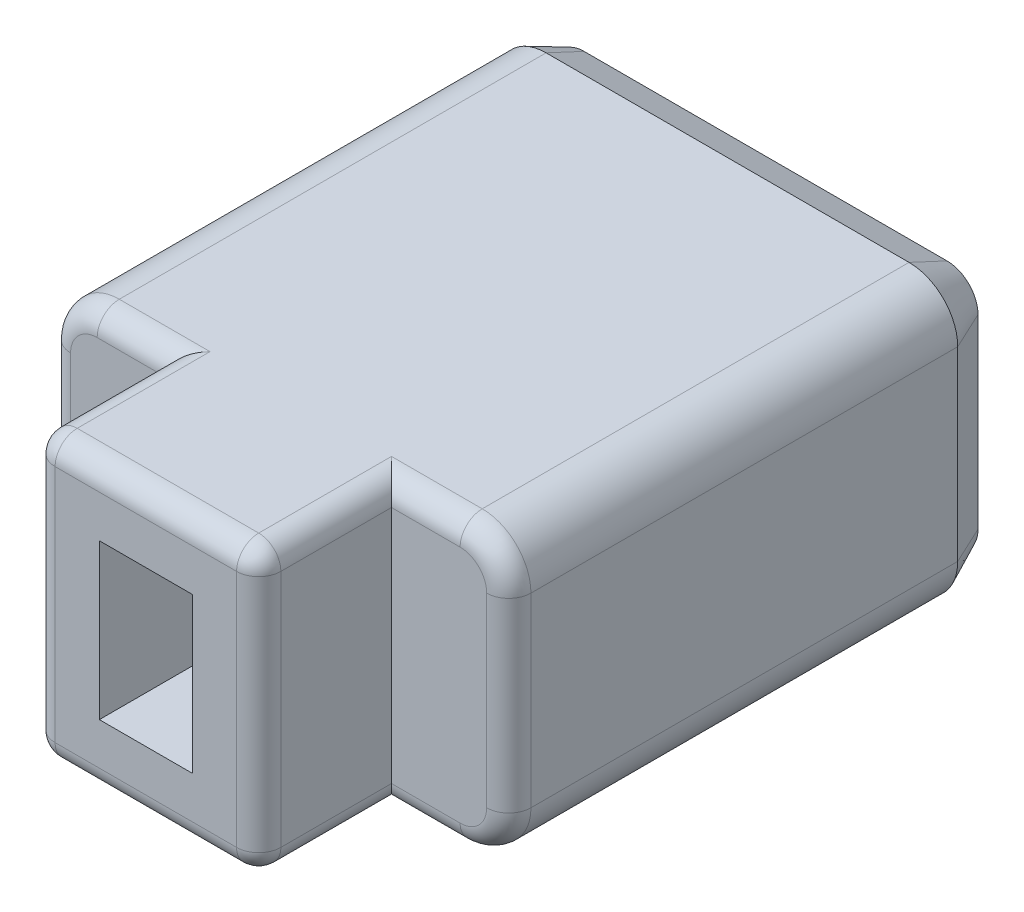
SolidWorks part; units mm, degrees
ref_plane "Plan de face" through (0, 0, 0) normal (0, 0, 1) x (1, 0, 0)
ref_plane "Plan de dessus" through (0, 0, 0) normal (0, 1, 0) x (1, 0, 0)
ref_plane "Plan de droite" through (0, 0, 0) normal (1, 0, 0) x (0, 0, -1)
sketch "Esquisse2" plane through (0, 0, 0) normal (0, 0, 1) x (1, 0, 0)
  line L1 (1.1, 0) -> (9.3, 0)
  line L2 (0, 1.1) -> (0, 5.3)
  line L3 (1.1, 6.4) -> (9.3, 6.4)
  line L4 (10.4, 1.1) -> (10.4, 5.3)
  arc A0 (9.3, 6.4) -> (10.4, 5.3) centre (9.3, 5.3) cw
  arc A1 (9.3, 0) -> (10.4, 1.1) centre (9.3, 1.1) ccw
  arc A2 (1.1, 0) -> (0, 1.1) centre (1.1, 1.1) cw
  arc A3 (0, 5.3) -> (1.1, 6.4) centre (1.1, 5.3) cw
  point P7 (10.4, 6.4)
  point P12 (0, 0)
  point P15 (0, 6.4)
  dimension "D3" = 1.1
  dimension "D1" = 10.4
  dimension "D2" = 6.4
extrude "Boss.-Extru.1" add sketch "Esquisse2" along normal blind 14
sketch "Esquisse3" plane through (0, 0, 14) normal (0, 0, 1) x (1, 0, 0)
  line L0 (0, 5.3) -> (0, 1.1) construction
  line L1 (4.15, 4.95) -> (6.25, 4.95)
  line L2 (4.15, 4.95) -> (4.15, 1.45)
  line L3 (4.15, 1.45) -> (6.25, 1.45)
  line L4 (6.25, 4.95) -> (6.25, 1.45)
  line L5 (10.4, 1.1) -> (10.4, 5.3) construction
  line L6 (9.3, 6.4) -> (1.1, 6.4) construction
  line L7 (1.1, 0) -> (9.3, 0) construction
  dimension "D1" = 2.1
  dimension "D2" = 3.5
  dimension "D3" = 4.15
  dimension "D4" = 4.15
  dimension "D5" = 1.45
  dimension "D6" = 1.45
extrude "Enlèv. mat.-Extru.1" cut sketch "Esquisse3" against normal blind 3
sketch "Esquisse4" plane through (0, 0, 14) normal (0, 0, 1) x (1, 0, 0)
  line L0 (2.65, 6.4) -> (2.65, 0)
  line L1 (9.3, 6.4) -> (1.1, 6.4) construction
  line L2 (1.1, 0) -> (9.3, 0) construction
  line L3 (2.65, 0) -> (7.75, 0)
  line L4 (7.75, 0) -> (7.75, 6.4)
  line L5 (7.75, 6.4) -> (2.65, 6.4)
  line L6 (4.15, 4.95) -> (4.15, 1.45) construction
  line L7 (6.25, 1.45) -> (6.25, 4.95) construction
  dimension "D1" = 1.5
  dimension "D2" = 1.5
extrude "Enlèv. mat.-Extru.2" cut sketch "Esquisse4" against normal blind 3 flip side to cut
fillet "Congé1" radius 0.5 18 edges at (8.525, 0, 11) (10.0778, 0.3222, 11) (10.4, 3.2, 11) (10.0778, 6.0778, 11) (1.875, 6.4, 11) (0.3222, 6.0778, 11) (1.875, 0, 11) (0.3222, 0.3222, 11) (7.75, 6.4, 12.5) (2.65, 6.4, 12.5) (7.75, 0, 12.5) (2.65, 0, 12.5) (2.65, 3.2, 14) (5.2, 6.4, 14) (7.75, 3.2, 14) (5.2, 0, 14) (8.525, 6.4, 11) (0, 3.2, 11)
chamfer "Chanfrein1" distance 0.4 angle 65 8 edges at (5.2, 0, 0) (10.0778, 0.3222, 0) (0.3222, 0.3222, 0) (10.4, 3.2, 0) (0, 3.2, 0) (10.0778, 6.0778, 0) (0.3222, 6.0778, 0) (5.2, 6.4, 0) first distance on face at (5.2, 3.2, 0)
sketch "Esquisse5" plane through (0, 0, 0) normal (0, 0, -1) x (-1, 0, 0)
  line L0 (-0.4, 5.3) -> (-10, 5.3) construction
  arc A0 (-9.3, 6) -> (-10, 5.3) centre (-9.3, 5.3) ccw construction
  text T0 "0" font "Century Gothic" height 4
extrude "Enlèv. mat.-Extru.3" cut sketch "Esquisse5" against normal blind 0.3
extrude "Boss.-Extru.2" add sketch "Esquisse5<2>" along normal blind 0.3 separate body
sketch "Esquisse5<2>" plane through (0, 0, 0) normal (0, 0, -1) x (-1, 0, 0) same geometry as "Esquisse5"
